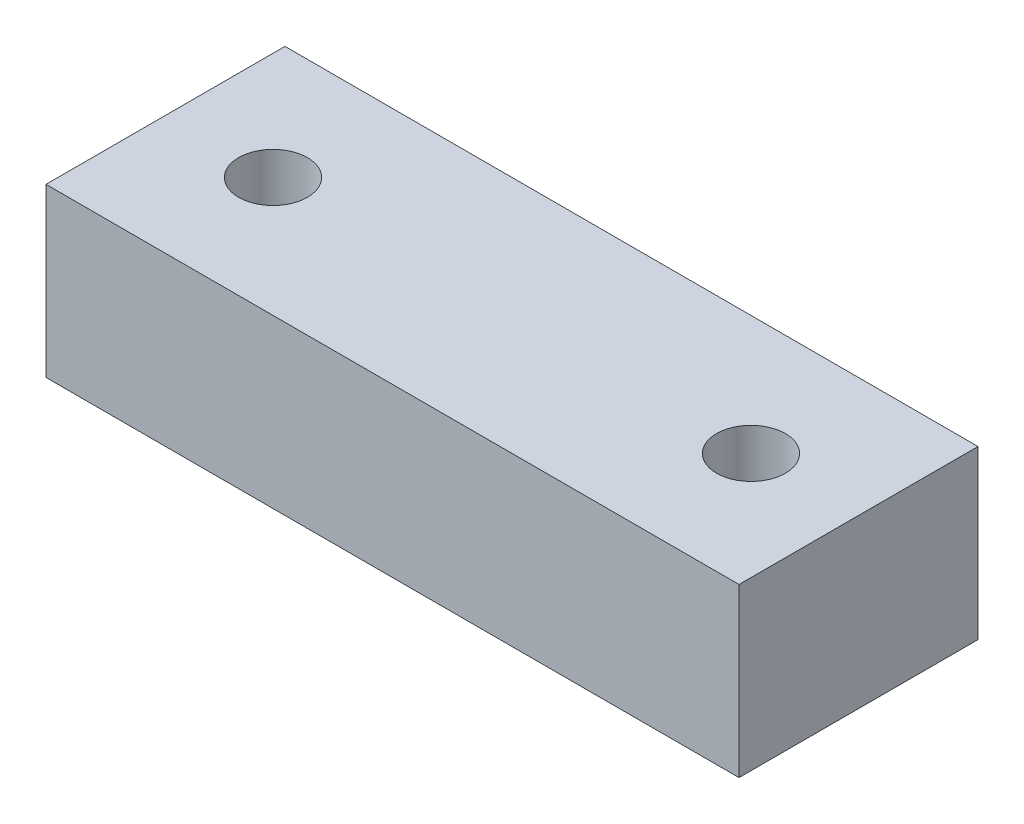
SolidWorks part; units mm, degrees
ref_plane "Front Plane" through (0, 0, 0) normal (0, 0, 1) x (1, 0, 0)
ref_plane "Top Plane" through (0, 0, 0) normal (0, 1, 0) x (1, 0, 0)
ref_plane "Right Plane" through (0, 0, 0) normal (1, 0, 0) x (0, 0, -1)
sketch "Sketch1" plane through (0, 0, 0) normal (0, 1, 0) x (1, 0, 0)
  line L1 (0, 0) -> (36.83, 0)
  line L2 (0, 0) -> (0, -12.7)
  line L3 (0, -12.7) -> (36.83, -12.7)
  line L4 (36.83, 0) -> (36.83, -12.7)
  point P9 (18.415, 0)
  point P10 (0, -6.35)
  dimension "D1" = 36.83
  dimension "D2" = 12.7
extrude "Boss-Extrude1" add sketch "Sketch1" along normal blind 8.89
hole_wizard "#27 (0.144) Diameter Hole1" positions "Sketch3" profile "Sketch2" hole size "#27" standard "ANSI Inch" end condition through all
sketch "Sketch3" plane through (0, 8.89, 0) normal (0, 1, 0) x (1, 0, 0)
  line L0 (36.83, 0) -> (0, 0) construction
  line L1 (0, 0) -> (0, -12.7) construction
  point P0 (5.715, -6.35)
  point P2 (31.115, -6.35)
  point P5 (18.415, 0)
  point P8 (0, -6.35)
  dimension "D1" = 25.4
  dimension "D2" = 12.7
  dimension "D3" = 0
  dimension "D4" = 0
sketch "Sketch2" plane through (5.715, 8.89, 6.35) normal (1, 0, 0) x (0, 0, 1)
  line L0 (0, 0) -> (0, 8.89)
  line L1 (0, 8.89) -> (1.8288, 8.89)
  line L2 (1.8288, 8.89) -> (1.8288, 0)
  line L5 (1.8288, 0) -> (0, 0)
  line L11 (0, -6.35) -> (0, 107.95) construction
  dimension "Thru Hole Dia." = 3.6576
  dimension "Thru Hole Depth" = 8.89
